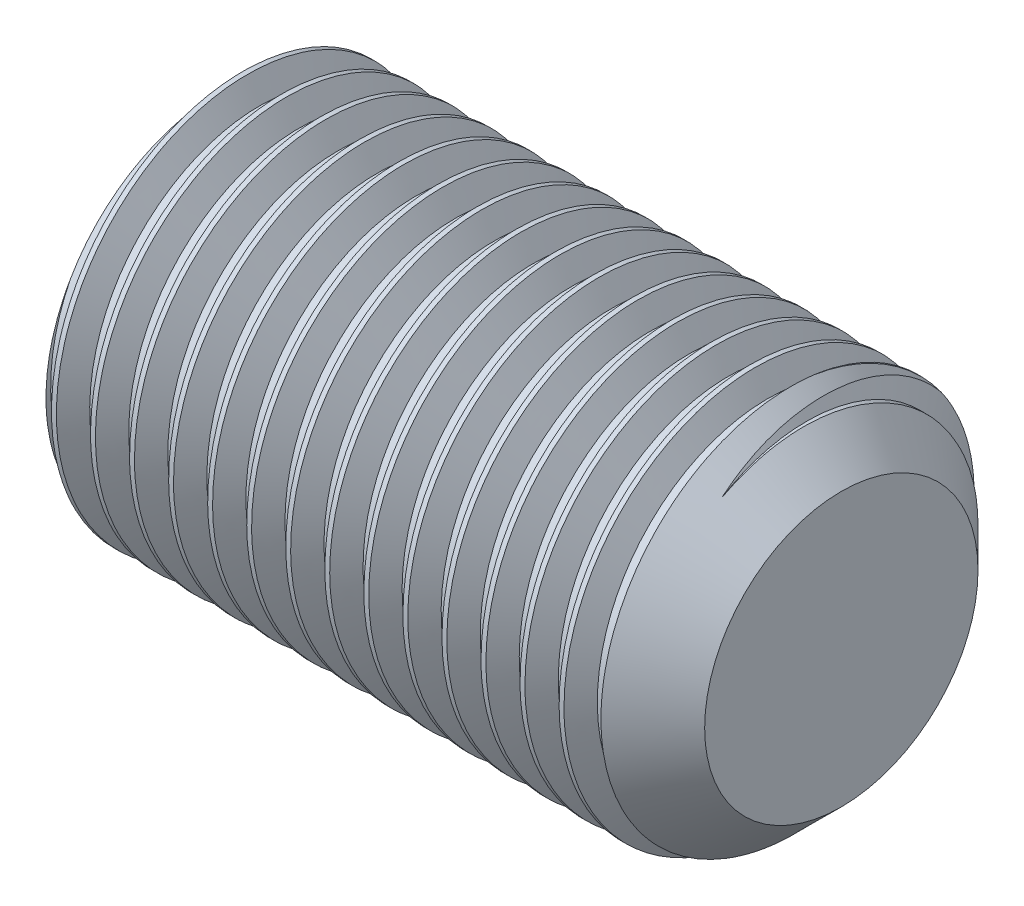
SolidWorks part; units mm, degrees
ref_plane "Front Plane" through (0, 0, 0) normal (0, 0, 1) x (1, 0, 0)
ref_plane "Top Plane" through (0, 0, 0) normal (0, 1, 0) x (1, 0, 0)
ref_plane "Right Plane" through (0, 0, 0) normal (1, 0, 0) x (0, 0, -1)
sketch "Sketch1" plane through (0, 0, 0) normal (0, 1, 0) x (1, 0, 0)
  line L0 (0, 4.2) -> (0.4, 5)
  line L1 (0, 0) -> (16, 0)
  line L2 (0, 0) -> (0, 4.2)
  line L3 (0.4, 5) -> (14.5, 5)
  line L4 (16, 0) -> (16, 3.5)
  line L5 (14.5, 5) -> (16, 3.5)
  point P1 (16, 5)
  point P2 (0, 5)
  dimension "D1" = 16
  dimension "D2" = 5
  dimension "D3" = 0.8
  dimension "D4" = 0.4
revolve "Revolve1" add sketch "Sketch1" angle 360 about L1
sketch "Sketch2" plane through (0, 0, 0) normal (-1, 0, 0) x (0, 0, 1)
  point P0 (0, 0)
hole_wizard "Ø5.0 (5) Diameter Hole1" positions "Sketch2" profile "Sketch3" hole size "Ø5.0" standard "ISO"
sketch "Sketch3" plane through (0, 0, 0) normal (0, 1, 0) x (0, 0, 1)
  line L0 (0, 0) -> (0, 7.5022)
  line L1 (0, 7.5022) -> (2.5, 6)
  line L2 (2.5, 6) -> (2.5, 0)
  line L5 (2.5, 0) -> (0, 0)
  line L10 (0, 7.5022) -> (-2.5, 6) construction
  line L11 (0, -6.35) -> (0, 107.95) construction
  point P3 (0, 0)
  dimension "Hole Dia." = 5
  dimension "Hole Depth" = 6
  dimension "Drill Angle" = 118
sketch "Sketch4" plane through (0, 0, 0) normal (-1, 0, 0) x (0, 0, 1)
  line L1 (1.4434, 2.5) -> (-1.4434, 2.5)
  line L2 (-1.4434, 2.5) -> (-2.8868, 0)
  line L3 (-2.8868, 0) -> (-1.4434, -2.5)
  line L4 (-1.4434, -2.5) -> (1.4434, -2.5)
  line L5 (1.4434, -2.5) -> (2.8868, 0)
  line L6 (2.8868, 0) -> (1.4434, 2.5)
  circle A0 centre (0, 0) radius 2.5 construction
  dimension "D1" = 5
extrude "Cut-Extrude1" cut sketch "Sketch4" against normal up to vertex (6 mm away) up to point (6, 0, -2.5)
thread "Thread1" pitch 1 start angle 0, offset 1, length 0, pitch 1, diameter 10
ref_plane "Plane1" through (-0.6, 0, -5) normal (0, -1, 0) x (0, 0, -1)
sketch "Thread Profile1" plane through (-0.6, 0, -5) normal (0, -1, 0) x (0, 0, -1)
  line L0 (0, 0) -> (0, 1) construction
  line L11 (0, 0) -> (0, 0.875)
  line L12 (0, 0.875) -> (-0.5413, 0.5625)
  line L13 (-0.5413, 0.5625) -> (-0.5413, 0.3125)
  line L15 (-0.5413, 0.3125) -> (0, 0)
  line L17 (-0.5413, 0.4375) -> (0, 0.4375) construction
  point P2 (0, 0)
  dimension "Pitch" = 1
  dimension "Profile_Angle" = 60
  dimension "Profile_Land" = 0.25
  dimension "Profile_Height" = 0.5413
